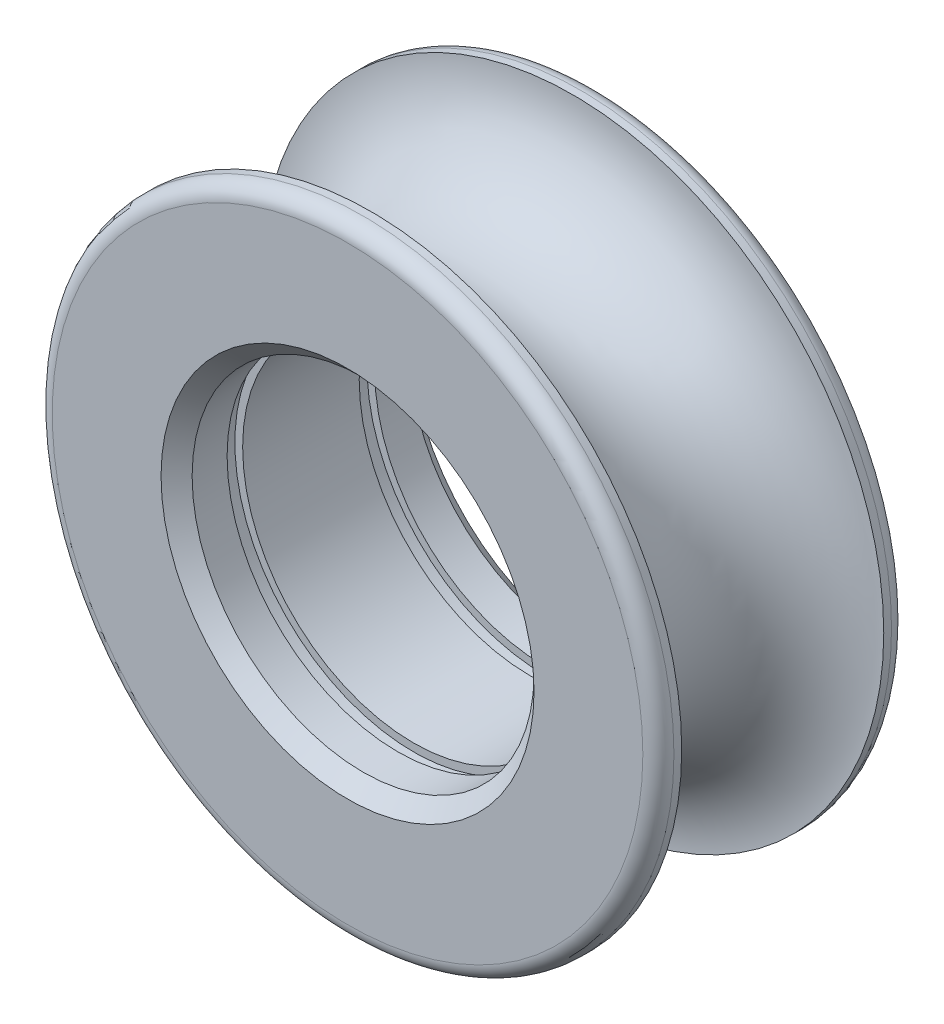
SolidWorks part; units mm, degrees
ref_plane "Front" through (0, 0, 0) normal (0, 0, 1) x (1, 0, 0)
ref_plane "Top" through (0, 0, 0) normal (0, 1, 0) x (1, 0, 0)
ref_plane "Right" through (0, 0, 0) normal (1, 0, 0) x (0, 0, -1)
sketch "Sketch1" plane through (0, 0, 0) normal (1, 0, 0) x (0, 0, -1)
  line L0 (0, 0) -> (10.1182, 0) construction
  line L1 (-7, 11) -> (7, 11)
  line L2 (8, 12) -> (8, 19)
  line L3 (7, 20) -> (6.5, 20)
  line L4 (-7, 11) -> (-8, 12)
  line L5 (0, 0) -> (0, 39.2002) construction
  line L6 (-7, 20) -> (-6.5, 20)
  line L7 (-8, 12) -> (-8, 19)
  line L8 (7, 11) -> (8, 12)
  arc A0 (-6.5, 20) -> (6.5, 20) centre (0, 20) ccw
  arc A1 (-7, 20) -> (-8, 19) centre (-7, 19) ccw
  arc A2 (8, 19) -> (7, 20) centre (7, 19) ccw
  point P4 (8, 11)
  point P9 (-8, 20)
  point P15 (-8, 11)
  point P18 (8, 20)
  dimension "D1" = 13
  dimension "D4" = 40
  dimension "D5" = 1
  dimension "D2" = 16
  dimension "D3" = 22
revolve "Revolve1" add sketch "Sketch1" angle 360 about L0
sketch "Sketch2" plane through (0, 0, 8) normal (0, 0, 1) x (1, 0, 0)
  circle A0 centre (0, 0) radius 11.5
  circle A1 centre (0, 0) radius 11
  dimension "D1" = 22
  dimension "D2" = 23
extrude "Cut-Extrude1" cut sketch "Sketch2" along normal blind 1 from offset 4.25 offset against normal yes
extrude "Cut-Extrude2" cut sketch "Sketch2<2>" against normal blind 1 from offset 11.75 offset against normal yes
sketch "Sketch2<2>" plane through (0, 0, 8) normal (0, 0, 1) x (1, 0, 0) same geometry as "Sketch2"
scale "Scale1" scale about centroid uniform scaling yes scale factor 1.013
